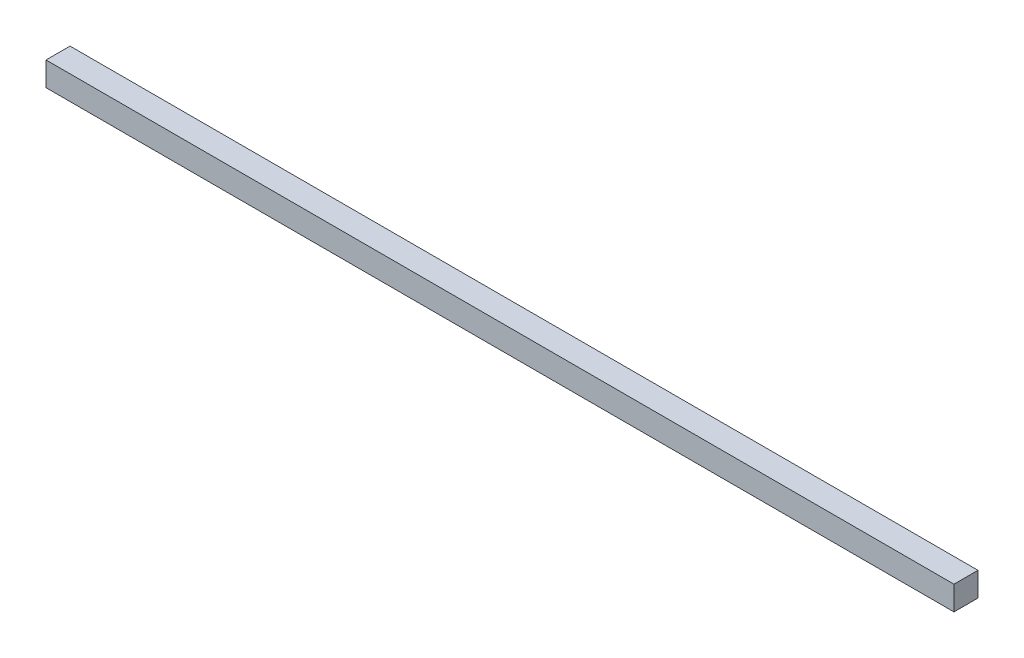
SolidWorks part; units mm, degrees
ref_plane "Front Plane" through (0, 0, 0) normal (0, 0, 1) x (1, 0, 0)
ref_plane "Top Plane" through (0, 0, 0) normal (0, 1, 0) x (1, 0, 0)
ref_plane "Right Plane" through (0, 0, 0) normal (1, 0, 0) x (0, 0, -1)
sketch "Sketch1" plane through (0, 0, 0) normal (0, 0, 1) x (1, 0, 0)
  line L0 (-170, 0) -> (170, 0) construction
  line L1 (0, -22.3452) -> (0, 22.3452) construction
  dimension "D1" = 340
sketch "Sketch2" plane through (0, 0, 0) normal (1, 0, 0) x (0, 0, -1)
  line L1 (-4.5, -4.5) -> (4.5, -4.5)
  line L2 (-4.5, -4.5) -> (-4.5, 4.5)
  line L3 (-4.5, 4.5) -> (4.5, 4.5)
  line L4 (4.5, -4.5) -> (4.5, 4.5)
  line L5 (-4.5, -4.5) -> (4.5, 4.5) construction
  line L6 (-4.5, 4.5) -> (4.5, -4.5) construction
  point P0 (0, 0)
  dimension "D1" = 9
extrude "Boss-Extrude1" add sketch "Sketch2" against normal up to vertex (170 mm away) and the other way up to vertex (170 mm away) up to point (-170, 0, 0) other way up to point (170, 0, 0)
